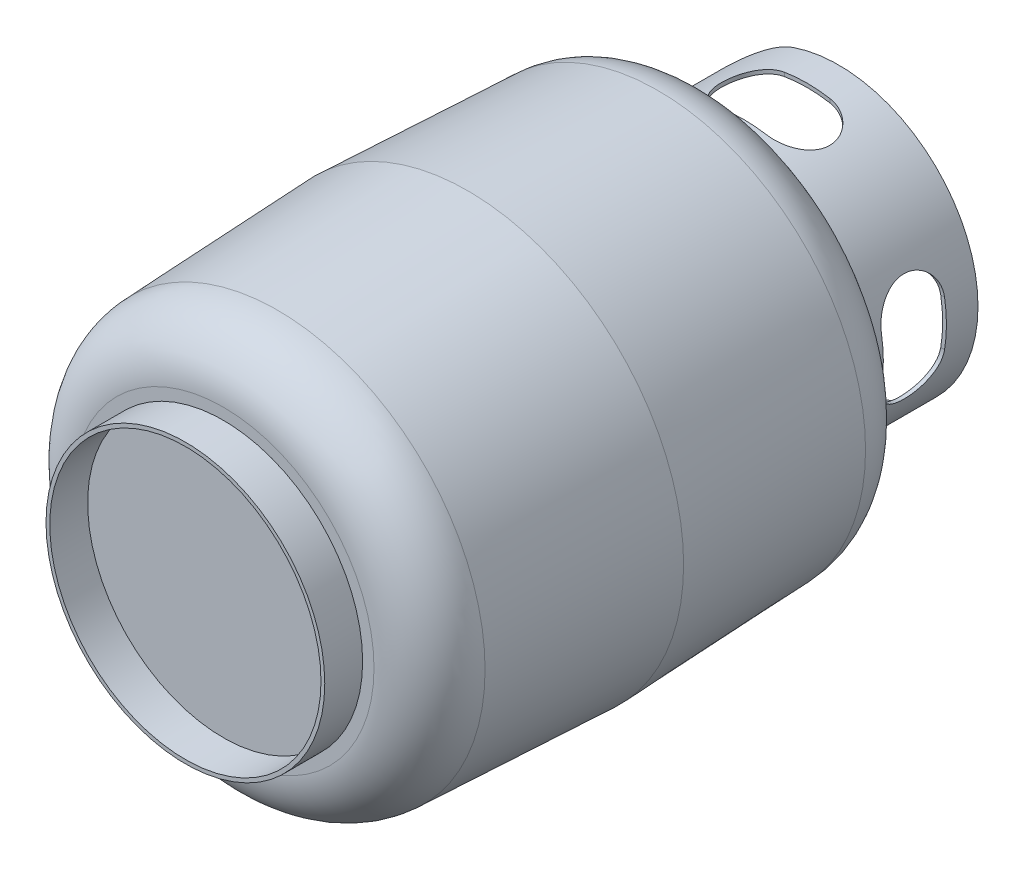
SolidWorks part; units mm, degrees
material "1060 Alloy"
ref_plane "Front Plane" through (0, 0, 0) normal (0, 0, 1) x (1, 0, 0)
ref_plane "Top Plane" through (0, 0, 0) normal (0, 1, 0) x (1, 0, 0)
ref_plane "Right Plane" through (0, 0, 0) normal (1, 0, 0) x (0, 0, -1)
sketch "Sketch1" plane through (0, 0, 0) normal (0, 1, 0) x (1, 0, 0)
  line L0 (0, 0) -> (-119.4219, 0)
  line L1 (-164.379, 43.0371) -> (-170.9593, 193.75)
  line L2 (-170.9593, 193.75) -> (-164.379, 344.4629)
  line L3 (-119.4219, 387.5) -> (-37, 387.5)
  line L4 (-25, 399.5) -> (-25, 403.5)
  line L5 (-25, 403.5) -> (0, 403.5)
  line L6 (0, 0) -> (0, 403.5) construction
  line L7 (0, 4) -> (-119.4219, 4)
  line L8 (-160.3828, 43.2116) -> (-166.9555, 193.75)
  line L9 (-166.9555, 193.75) -> (-160.3828, 344.2884)
  line L10 (-119.4219, 383.5) -> (-37, 383.5)
  line L11 (-21, 399.5) -> (-21, 399.5)
  line L12 (-21, 399.5) -> (0, 399.5)
  line L13 (0, 399.5) -> (0, 403.5)
  line L14 (0, 4) -> (0, 0)
  arc A0 (-119.4219, 0) -> (-164.379, 43.0371) centre (-119.4219, 45) cw
  arc A1 (-164.379, 344.4629) -> (-119.4219, 387.5) centre (-119.4219, 342.5) cw
  arc A2 (-37, 387.5) -> (-25, 399.5) centre (-37, 399.5) ccw
  arc A3 (-119.4219, 4) -> (-160.3828, 43.2116) centre (-119.4219, 45) cw
  arc A4 (-160.3828, 344.2884) -> (-119.4219, 383.5) centre (-119.4219, 342.5) cw
  arc A5 (-37, 383.5) -> (-21, 399.5) centre (-37, 399.5) ccw
  point P10 (-162.5, 0)
  point P13 (-162.5, 387.5)
  dimension "D5" = 45
  dimension "D6" = 12
  dimension "D1" = 387.5
  dimension "D2" = 162.5
  dimension "D3" = 92.5
  dimension "D4" = 92.5
  dimension "D8" = 20
  dimension "D9" = 25
  dimension "D7" = 4
revolve "Revolve1" add sketch "Sketch1" angle 360 about L6
sketch "Sketch2" plane through (0, 0, -403.5) normal (0, 0, -1) x (-1, 0, 0)
  circle A2 centre (0, 0) radius 21
  circle A3 centre (0, 0) radius 21
  dimension "D1" = 4
extrude "Cut-Extrude1" cut sketch "Sketch2" against normal blind 4 contours A3
sketch "Sketch3" plane through (0, 0, -387.5) normal (0, 0, -1) x (-1, 0, 0)
  line L0 (0, 0) -> (114.836, 0) construction
  line L1 (0, 0) -> (63.3354, 90.4523) construction
  line L2 (0, 0) -> (63.3354, -90.4523) construction
  line L3 (61.6147, 87.9948) -> (63.3354, 90.4523)
  line L4 (61.6147, -87.9948) -> (63.3354, -90.4523)
  arc A1 (63.3354, 90.4523) -> (63.3354, -90.4523) centre (0, 0) ccw
  circle A2 centre (0, 0) radius 107.4219
  arc A3 (61.6147, 87.9948) -> (61.6147, -87.9948) centre (0, 0) ccw
  circle A5 centre (0, 0) radius 107.4219 construction
  circle A6 centre (0, 0) radius 110.4219 construction
  dimension "D3" = 55
  dimension "D4" = 55
  dimension "D1" = 12
  dimension "D2" = 3
extrude "Boss-Extrude1" add sketch "Sketch3" along normal blind 100
fillet "Fillet1" radius 30 2 edges at (-62.475, -89.2236, -487.5) (-62.475, 89.2236, -487.5)
sketch "Sketch4" plane through (0, 0, 0) normal (0, 1, 0) x (1, 0, 0)
  line L0 (18, 437.5) -> (-18, 437.5) construction
  line L1 (18, 412.5) -> (-18, 412.5)
  line L2 (18, 462.5) -> (-18, 462.5)
  line L3 (110.4219, 487.5) -> (-36.3785, 487.5) construction
  arc A0 (18, 412.5) -> (18, 462.5) centre (18, 437.5) ccw
  arc A1 (-18, 462.5) -> (-18, 412.5) centre (-18, 437.5) ccw
  point P2 (0, 437.5)
  dimension "D1" = 25
  dimension "D2" = 36
  dimension "D3" = 18
  dimension "D4" = 50
extrude "Cut-Extrude2" cut sketch "Sketch4" against normal through all and the other way through all contours L2 A1 L1 A0
sketch "Sketch7" plane through (0, 0, 0) normal (1, 0, 0) x (0, 0, -1)
  line L0 (437.5, 18) -> (437.5, -18) construction
  line L1 (462.5, 18) -> (462.5, -18)
  line L2 (412.5, 18) -> (412.5, -18)
  line L3 (487.5, -110.4219) -> (487.5, 110.4219) construction
  arc A0 (462.5, 18) -> (412.5, 18) centre (437.5, 18) ccw
  arc A1 (412.5, -18) -> (462.5, -18) centre (437.5, -18) ccw
  point P2 (437.5, 0)
  dimension "D1" = 25
  dimension "D2" = 36
  dimension "D3" = 18
  dimension "D4" = 50
extrude "Cut-Extrude3" cut sketch "Sketch7" along normal through all
sketch "Sketch8" plane through (0, 0, 0) normal (0, 0, 1) x (1, 0, 0)
  circle A1 centre (0, 0) radius 110.4219
  circle A2 centre (0, 0) radius 107.4219
  circle A3 centre (0, 0) radius 107.4219
  dimension "D1" = 12
  dimension "D2" = 3
extrude "Boss-Extrude2" add sketch "Sketch8" along normal blind 30
equation "\"A\"= 325mm"
equation "\"B\"= 387.5mm"
